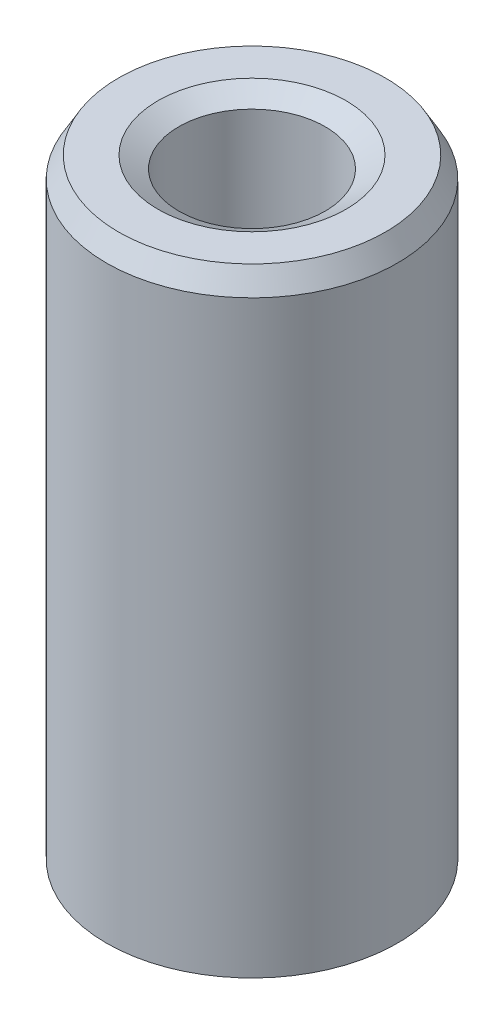
SolidWorks part; units mm, degrees
ref_plane "Front Plane" through (0, 0, 0) normal (0, 0, 1) x (1, 0, 0)
ref_plane "Top Plane" through (0, 0, 0) normal (0, 1, 0) x (1, 0, 0)
ref_plane "Right Plane" through (0, 0, 0) normal (1, 0, 0) x (0, 0, -1)
sketch "Sketch1" plane through (0, 0, 0) normal (0, 1, 0) x (1, 0, 0)
  circle A0 centre (0, 0) radius 25
  dimension "SLEEVE_OD" = 50
extrude "Boss-Extrude1" add sketch "Sketch1" along normal blind 106.8373
sketch "Sketch2" plane through (0, 0, 0) normal (0, 1, 0) x (1, 0, 0)
  circle A0 centre (0, 0) radius 12.5783
  dimension "BORE_D" = 25.1566
extrude "Cut-Extrude1" cut sketch "Sketch2" along normal through all
chamfer "Chamfer1" distance 3.5831 angle 30 4 edges at (0, 106.8373, 12.5783) (0, 0, 12.5783) (0, 0, 25) (0, 106.8373, 25) first distance on face at (0, 106.8373, 12.5783) first distance on face at (0, 0, 12.5783) first distance on face at (0, 106.8373, 25)
